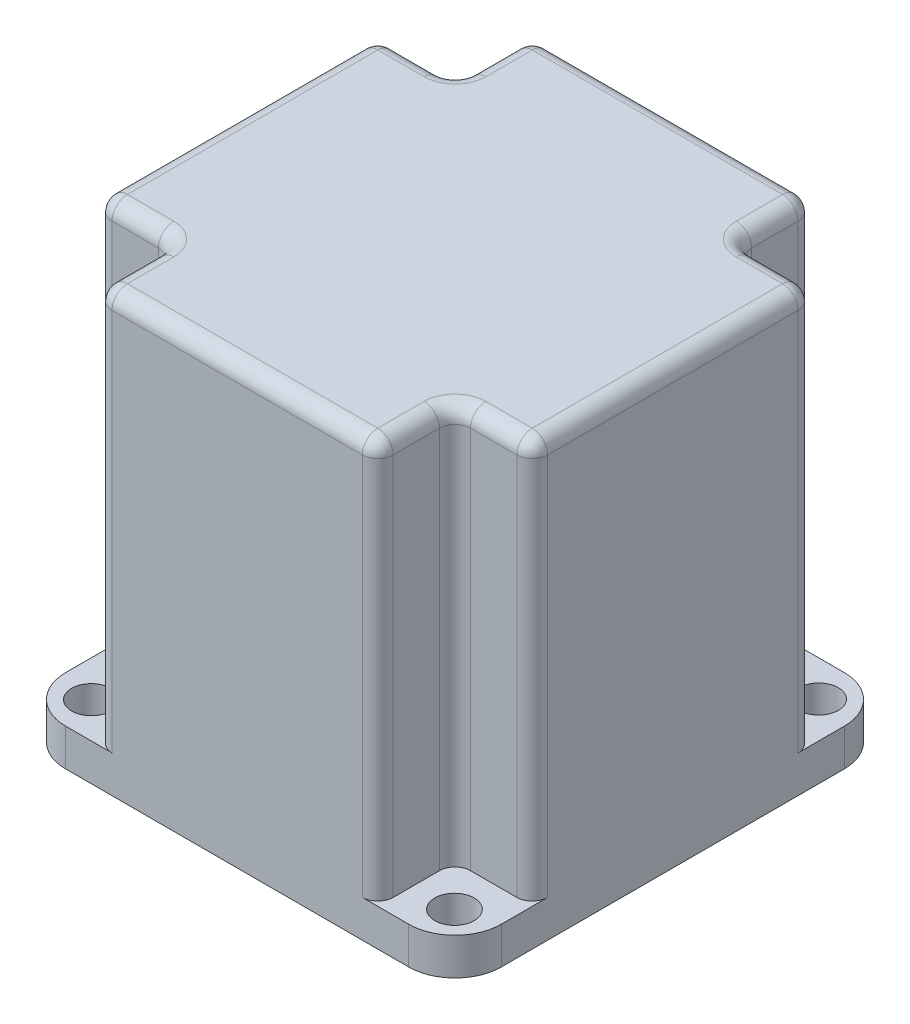
SolidWorks part; units mm, degrees
ref_plane "前视基准面" through (0, 0, 0) normal (0, 0, 1) x (1, 0, 0)
ref_plane "上视基准面" through (0, 0, 0) normal (0, 1, 0) x (1, 0, 0)
ref_plane "右视基准面" through (0, 0, 0) normal (1, 0, 0) x (0, 0, -1)
other "Configuration Table"
sketch "草图1" plane through (0, 0, 0) normal (0, 1, 0) x (1, 0, 0)
  line L0 (-28.2, 0) -> (28.2, 0) construction
  line L1 (-22.2, 28.2) -> (22.2, 28.2)
  line L2 (-28.2, 22.2) -> (-28.2, -22.2)
  line L3 (-22.2, -28.2) -> (22.2, -28.2)
  line L4 (28.2, 22.2) -> (28.2, -22.2)
  line L5 (-28.2, 28.2) -> (28.2, -28.2) construction
  line L6 (-28.2, -28.2) -> (28.2, 28.2) construction
  line L7 (0, 28.2) -> (0, -28.2) construction
  line L8 (-2.6458, 3) -> (2.6458, 3)
  circle A0 centre (0, 0) radius 19.05
  circle A1 centre (-23.5, 23.57) radius 2.55
  circle A2 centre (-23.5, -23.57) radius 2.55
  circle A3 centre (23.5, -23.57) radius 2.55
  circle A4 centre (23.5, 23.57) radius 2.55
  arc A5 (22.2, 28.2) -> (28.2, 22.2) centre (22.2, 22.2) cw
  arc A6 (22.2, -28.2) -> (28.2, -22.2) centre (22.2, -22.2) ccw
  arc A7 (-28.2, -22.2) -> (-22.2, -28.2) centre (-22.2, -22.2) ccw
  arc A8 (-22.2, 28.2) -> (-28.2, 22.2) centre (-22.2, 22.2) ccw
  circle A9 centre (0, 0) radius 4
  point P0 (0, 0)
  dimension "D3" = 38.1
  dimension "D5" = 47
  dimension "D6" = 5.1
  dimension "D7" = 6
  dimension "D8" = 8
  dimension "D1" = 56.4
  dimension "D2" = 56.4
  dimension "D4" = 47.14
  dimension "D9" = 3
extrude "凸台-拉伸1" add sketch "草图1" along normal blind 56.4 contours A0 | L1 A8 L2 A7 L3 A6 L4 A5 A4 A3 A0 A1 A2 | A1 | A4 | A3 | A2 | L8 A9 | L8 A9 region at (0, 0, -27.4024) region at (0, 0, -3.4046) region at (0, 0, 0.2647) region at (-18.5112, 0, 0) region at (-23.5, 0, -23.57) region at (-23.5, 0, 23.57) region at (23.5, 0, 23.57) region at (23.5, 0, -23.57)
extrude "凸台-拉伸2" add sketch "草图1<3>" against normal blind 1.6 contours A0 region at (-18.5112, 0, 0)
sketch "草图1<3>" plane through (0, 0, 0) normal (0, 1, 0) x (1, 0, 0) same geometry as "草图1"
extrude "切除-拉伸1" cut sketch "草图1<4>" along normal blind 4.8 contours A3 | A1 | A4 | A2 region at (-23.5, 0, -23.57) region at (23.5, 0, 23.57) region at (23.5, 0, -23.57)
sketch "草图1<4>" plane through (0, 0, 0) normal (0, 1, 0) x (1, 0, 0) same geometry as "草图1"
extrude "凸台-拉伸3" add sketch "草图1<5>" against normal blind 20.6 contours L8 A9 region at (0, 0, 0.2647)
sketch "草图1<5>" plane through (0, 0, 0) normal (0, 1, 0) x (1, 0, 0) same geometry as "草图1"
sketch "草图4" plane through (0, 56.4, 0) normal (0, 1, 0) x (1, 0, 0)
  line L0 (-28.2, 22.2) -> (-28.2, -22.2) construction
  line L1 (-28.2, 28.2) -> (-18.2, 28.2)
  line L2 (-28.2, 28.2) -> (-28.2, 18.2)
  line L3 (-28.2, 18.2) -> (-18.2, 18.2)
  line L4 (-18.2, 28.2) -> (-18.2, 18.2)
  line L5 (-22.2, 28.2) -> (22.2, 28.2) construction
  line L6 (-28.2, 0) -> (28.2, 0) construction
  line L7 (0, 28.2) -> (0, -28.2) construction
  line L8 (-28.2, -18.2) -> (-18.2, -18.2)
  line L9 (-18.2, -28.2) -> (-18.2, -18.2)
  line L10 (-28.2, -28.2) -> (-18.2, -28.2)
  line L11 (-28.2, -28.2) -> (-28.2, -18.2)
  line L12 (28.2, -28.2) -> (28.2, -18.2)
  line L13 (28.2, -28.2) -> (18.2, -28.2)
  line L14 (18.2, -28.2) -> (18.2, -18.2)
  line L15 (28.2, -18.2) -> (18.2, -18.2)
  line L16 (28.2, 18.2) -> (18.2, 18.2)
  line L17 (18.2, 28.2) -> (18.2, 18.2)
  line L18 (28.2, 28.2) -> (18.2, 28.2)
  line L19 (28.2, 28.2) -> (28.2, 18.2)
  line L20 (28.2, 22.2) -> (28.2, -22.2) construction
  line L21 (-22.2, -28.2) -> (22.2, -28.2) construction
  dimension "D1" = 10
  dimension "D2" = 10
extrude "切除-拉伸3" cut sketch "草图4" against normal blind 51.6
fillet "圆角3" radius 2 20 edges at (18.2, 56.4, 23.2) (23.2, 56.4, 18.2) (-18.2, 56.4, 23.2) (-23.2, 56.4, 18.2) (-23.2, 56.4, -18.2) (-18.2, 56.4, -23.2) (18.2, 56.4, -23.2) (23.2, 56.4, -18.2) (-28.2, 30.6, 18.2) (-18.2, 30.6, 18.2) (-18.2, 30.6, 28.2) (18.2, 30.6, 28.2) (18.2, 30.6, 18.2) (28.2, 30.6, 18.2) (28.2, 30.6, -18.2) (18.2, 30.6, -18.2) (18.2, 30.6, -28.2) (-28.2, 30.6, -18.2) (-18.2, 30.6, -18.2) (-18.2, 30.6, -28.2)
fillet "圆角4" radius 2 12 edges at (-27.6142, 55.8142, -17.6142) (-27.6142, 55.8142, 17.6142) (-17.6142, 55.8142, -27.6142) (17.6142, 55.8142, -27.6142) (27.6142, 55.8142, -17.6142) (27.6142, 55.8142, 17.6142) (-17.6142, 55.8142, 27.6142) (17.6142, 55.8142, 27.6142) (-28.2, 56.4, 0) (0, 56.4, -28.2) (28.2, 56.4, 0) (0, 56.4, 28.2)
